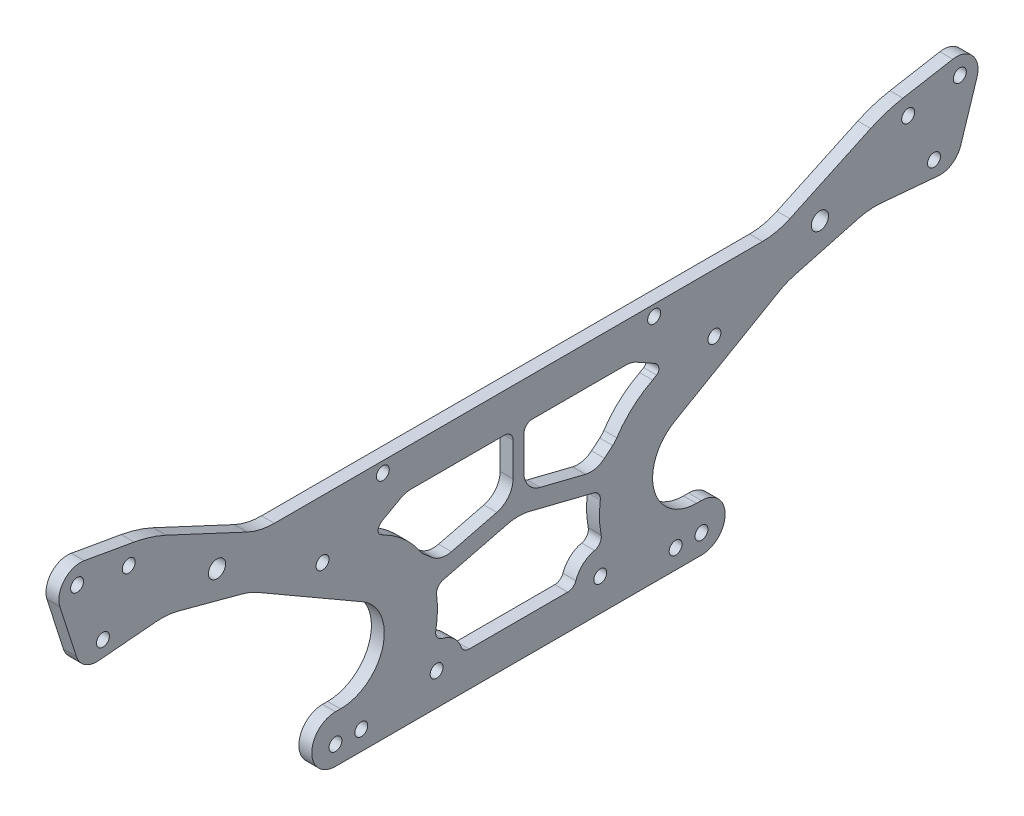
SolidWorks part; units mm, degrees
material "1060 Alloy"
ref_plane "Front Plane" through (0, 0, 0) normal (0, 0, 1) x (1, 0, 0)
ref_plane "Top Plane" through (0, 0, 0) normal (0, 1, 0) x (1, 0, 0)
ref_plane "Right Plane" through (0, 0, 0) normal (1, 0, 0) x (0, 0, -1)
sketch "Sketch1" plane through (0, 0, 0) normal (1, 0, 0) x (0, 0, -1)
  line L0 (0, 0) -> (0, 8) construction
  line L1 (-42.5, 0) -> (42.5, 0)
  line L2 (42.5, 11) -> (41.3351, 11)
  line L3 (36.2441, 30) -> (62.2249, 45)
  line L7 (-60, 56) -> (60, 56)
  line L8 (18.0221, 29.1156) -> (1.25, 33.3106)
  line L9 (1.25, 33.3106) -> (1.25, 47)
  line L10 (1.25, 47) -> (26.25, 47)
  line L11 (18.0221, 29.1156) -> (22.4667, 32.8451)
  line L12 (34.109, 42.6142) -> (26.25, 47)
  line L13 (0, 0) -> (0, 8)
  line L14 (60, 56) -> (85.3766, 67.8333)
  line L15 (85.3766, 67.8333) -> (109.012, 72.0009)
  line L16 (62.2249, 45) -> (81.5434, 50.1764)
  line L17 (81.5434, 50.1764) -> (101.4673, 48.4333)
  line L18 (101.4673, 48.4333) -> (109.012, 72.0009)
  line L19 (0, 29.5) -> (0, 101.8162) construction
  line L20 (0, 29.5) -> (0, 56)
  line L21 (19, 8) -> (20.4142, 8)
  line L22 (33.1258, 41.7891) -> (34.109, 42.6142)
  line L23 (-18.0221, 29.1156) -> (-22.4667, 32.8451)
  line L24 (-33.1258, 41.7891) -> (-34.109, 42.6142)
  line L25 (-34.109, 42.6142) -> (-26.25, 47)
  line L26 (-1.25, 47) -> (-26.25, 47)
  line L27 (-1.25, 33.3106) -> (-1.25, 47)
  line L28 (-18.0221, 29.1156) -> (-1.25, 33.3106)
  line L31 (-60, 56) -> (-85.3766, 67.8333)
  line L32 (-85.3766, 67.8333) -> (-109.012, 72.0009)
  line L33 (-101.4673, 48.4333) -> (-109.012, 72.0009)
  line L34 (-81.5434, 50.1764) -> (-101.4673, 48.4333)
  line L35 (-36.2441, 30) -> (-62.2249, 45)
  line L36 (-62.2249, 45) -> (-81.5434, 50.1764)
  line L37 (-42.5, 11) -> (-41.3351, 11)
  line L38 (-32.4094, 629.8778) -> (438.9239, 629.8778) construction
  line L39 (10, 56) -> (20, 58)
  line L40 (59.5566, 58) -> (84.77, 69.7572)
  line L41 (-60, 58) -> (0, 58)
  line L42 (84.77, 69.7572) -> (111.9267, 74.5457)
  line L43 (103.372, 47.8235) -> (111.9267, 74.5457)
  line L44 (20, 58) -> (59.5566, 58)
  line L45 (-60, 58) -> (60, 58) construction
  line L46 (59.1548, 57.8126) -> (84.77, 69.7572) construction
  line L47 (36.5, 4.5) -> (42.5, 4.5) construction
  line L48 (90.5, 64.3841) -> (102.5, 66.5) construction
  line L49 (-103.372, 47.8235) -> (-111.9267, 74.5457)
  line L50 (-84.77, 69.7572) -> (-111.9267, 74.5457)
  line L51 (-59.5566, 58) -> (-84.77, 69.7572)
  line L52 (-20, 58) -> (-59.5566, 58)
  line L53 (-10, 56) -> (-20, 58)
  line L54 (-103.372, 47.8235) -> (-101.4673, 48.4333)
  line L55 (101.4673, 48.4333) -> (103.372, 47.8235)
  line L57 (17.5858, 8) -> (19, 8)
  line L59 (-13.0301, 8.1) -> (13.0301, 8.1)
  line L61 (0, 29.3969) -> (19.3116, 24.5668)
  line L62 (0, 29.3969) -> (-19.3116, 24.5668)
  arc A0 (42.5, 0) -> (42.5, 11) centre (42.5, 5.5) ccw
  arc A1 (41.3351, 11) -> (36.2441, 30) centre (41.3351, 21.1821) cw
  arc A3 (22.4667, 32.8451) -> (33.1258, 41.7891) centre (41.3351, 21.1821) cw
  arc A5 (-22.4667, 32.8451) -> (-33.1258, 41.7891) centre (-41.3351, 21.1821) ccw
  arc A7 (-41.3351, 11) -> (-36.2441, 30) centre (-41.3351, 21.1821) ccw
  arc A8 (-42.5, 0) -> (-42.5, 11) centre (-42.5, 5.5) cw
  circle A9 centre (31.5, 53.5) radius 1.5
  circle A10 centre (45.5, 42.5) radius 1.5
  circle A11 centre (70, 53.5) radius 2
  circle A12 centre (90.5, 64.3841) radius 1.5
  circle A13 centre (102.5, 66.5) radius 1.5
  circle A14 centre (96.5, 52.5) radius 1.5
  circle A15 centre (42.5, 4.5) radius 1.5
  circle A16 centre (36.5, 4.5) radius 1.5
  circle A17 centre (19, 7.5) radius 1.5
  circle A19 centre (-36.5, 4.5) radius 1.5
  circle A20 centre (-42.5, 4.5) radius 1.5
  circle A21 centre (-96.5, 52.5) radius 1.5
  circle A22 centre (-102.5, 66.5) radius 1.5
  circle A23 centre (-90.5, 64.3841) radius 1.5
  circle A24 centre (-70, 53.5) radius 2
  circle A25 centre (-45.5, 42.5) radius 1.5
  circle A26 centre (-31.5, 53.5) radius 1.5
  circle A27 centre (-19, 7.5) radius 1.5
  arc A28 (19.7391, 13.4543) -> (19.3116, 24.5668) centre (41.0866, 19.8399) cw
  arc A29 (-19.7391, 13.4543) -> (-19.3116, 24.5668) centre (-41.0866, 19.8399) ccw
  arc A32 (19.7391, 13.4543) -> (13.0301, 8.1) centre (19, 7.5) ccw
  arc A33 (-13.0301, 8.1) -> (-19.7391, 13.4543) centre (-19, 7.5) ccw
  point P11 (48, 5.5)
  point P14 (19.7391, 13.5019)
  point P24 (-19.7817, 13.4543)
  dimension "D1" = 5.5
  dimension "D33" = 3
  dimension "D34" = 3
  dimension "D35" = 3
  dimension "D36" = 3
  dimension "D37" = 3
  dimension "D38" = 4
  dimension "D39" = 3
  dimension "D40" = 3
  dimension "D41" = 3
  dimension "D42" = 4.5
  dimension "D43" = 3
  dimension "D44" = 17.5
  dimension "D45" = 0
  dimension "D46" = 38
  dimension "D47" = 90.5
  dimension "D48" = 14
  dimension "D49" = 11
  dimension "D50" = 24.5
  dimension "D51" = 11
  dimension "D52" = 12
  dimension "D53" = 96.5
  dimension "D54" = 26.5
  dimension "D55" = 1
  dimension "D56" = 14
  dimension "D59" = 12
  dimension "D60" = 12
  dimension "D2" = 30
  dimension "D3" = 48
  dimension "D5" = 21.5
  dimension "D7" = 19
  dimension "D9" = 2.5
  dimension "D10" = 56
  dimension "D11" = 9
  dimension "D12" = 25
  dimension "D13" = 9
  dimension "D14" = 21
  dimension "D15" = 60
  dimension "D16" = 28
  dimension "D17" = 24
  dimension "D18" = 155
  dimension "D19" = 170
  dimension "D20" = 19
  dimension "D21" = 30
  dimension "D22" = 15
  dimension "D23" = 20
  dimension "D24" = 20
  dimension "D25" = 160
  dimension "D26" = 40
  dimension "D27" = 2
  dimension "D30" = 10
  dimension "D31" = 10
  dimension "D32" = 6
  dimension "D29" = 2
extrude "Boss-Extrude1" add sketch "Sketch1" along normal blind 3 contours A8 L1 A0 L2 A1 L3 L16 L17 L18 L15 L14 L7 L31 L32 L33 L34 L36 L35 A7 L37 A26 A24 A22 region at (0, 5.5, 45.7039)
fillet "Fillet1" radius 5 2 edges at (1.5, 32.8451, 22.4667) (1.5, 29.1156, 18.0221)
fillet "Fillet2" radius 10 1 edges at (1.5, 29.3969, 0)
fillet "Fillet3" radius 2 6 edges at (1.5, 24.5668, 19.3116) (1.5, 24.5668, -19.3116) (1.5, 8.1, -13.0301) (1.5, 13.4543, -19.7391) (1.5, 13.4543, 19.7391) (1.5, 8.1, 13.0301)
fillet "Fillet4" radius 5 1 edges at (1.5, 33.3106, 1.25)
fillet "Fillet5" radius 2 1 edges at (1.5, 47, 1.25)
fillet "Fillet6" radius 5 1 edges at (1.5, 47, 26.25)
fillet "Fillet7" radius 15 1 edges at (1.5, 45, 62.2249)
fillet "Fillet8" radius 15 2 edges at (1.5, 56, 60) (1.5, 50.1764, 81.5434)
fillet "Fillet9" radius 30 1 edges at (1.5, 67.8333, 85.3766)
fillet "Fillet10" radius 5 2 edges at (1.5, 48.4333, 101.4673) (1.5, 72.0009, 109.012)
sketch "Sketch2" plane through (0, 0, 0) normal (-1, 0, 0) x (0, 0, 1)
  line L3 (34.109, 42.6142) -> (31.1551, 40.8902)
  line L8 (31.1551, 40.8902) -> (35.4351, 42.4869)
  line L9 (35.4351, 42.4869) -> (34.109, 42.6142)
  arc A2 (33.1258, 41.7891) -> (22.8379, 33.4254) centre (41.3351, 21.1821) ccw construction
extrude "Boss-Extrude2" add sketch "Sketch2" against normal blind 3
fillet "Fillet11" radius 1 1 edges at (1.5, 42.6142, 34.109) second distance 2 first distance on face at (1.5, 41.7522, 32.6321)
ref_plane "Plane1" through (0, 0, 0) normal (0, 0, 1) x (1, 0, 0)
sketch "Sketch3" plane through (0, 0, 0) normal (-1, 0, 0) x (0, 0, 1)
  line L0 (0, 0) -> (0, 75.072)
  line L1 (0, 75.072) -> (-134.9122, 75.072)
  line L2 (-134.9122, 75.072) -> (-134.9122, -12.2464)
  line L3 (-134.9122, -12.2464) -> (0, 0)
extrude "Cut-Extrude1" cut sketch "Sketch3" against normal blind 3
mirror "Mirror3" about plane through (0, 0, 0) normal (0, 0, 1) of bodies 107 103
